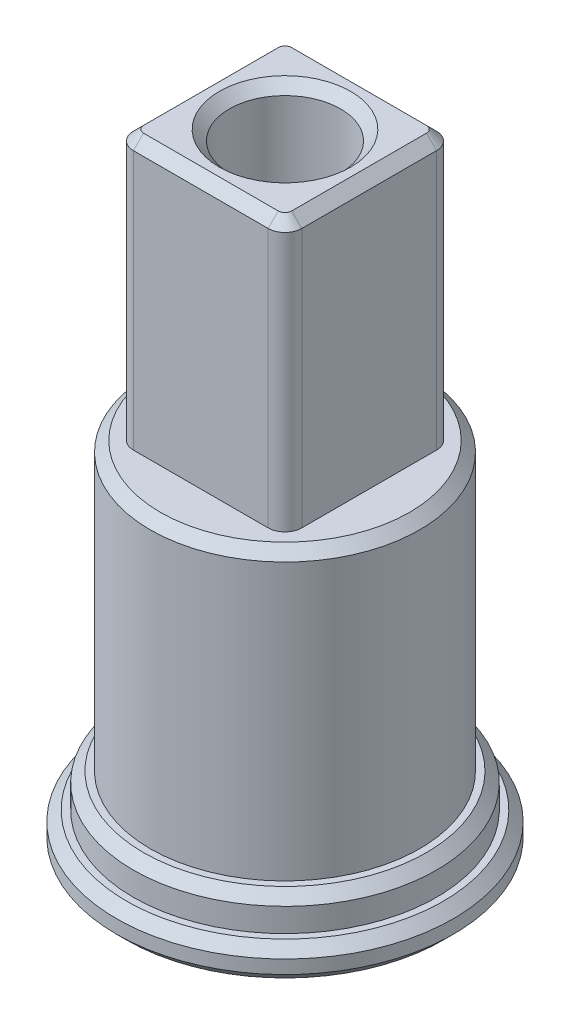
SolidWorks part; units mm, degrees
material "보통 탄소강"
ref_plane "정면" through (0, 0, 0) normal (0, 0, 1) x (1, 0, 0)
ref_plane "윗면" through (0, 0, 0) normal (0, 1, 0) x (1, 0, 0)
ref_plane "우측면" through (0, 0, 0) normal (1, 0, 0) x (0, 0, -1)
sketch "스케치1" plane through (0, 0, 0) normal (0, 1, 0) x (1, 0, 0)
  line L1 (2.5, -2.5) -> (-2.5, -2.5)
  line L2 (2.5, -2.5) -> (2.5, 2.5)
  line L3 (2.5, 2.5) -> (-2.5, 2.5)
  line L4 (-2.5, -2.5) -> (-2.5, 2.5)
  line L5 (2.5, -2.5) -> (-2.5, 2.5) construction
  line L6 (2.5, 2.5) -> (-2.5, -2.5) construction
  circle A0 centre (0, 0) radius 4
  circle A1 centre (0, 0) radius 5
  circle A2 centre (0, 0) radius 4.5
  dimension "D1" = 8
  dimension "D2" = 10
  dimension "D3" = 9
  dimension "D4" = 5
extrude "보스-돌출1" add sketch "스케치1" along normal blind 1 contours A1 A2 region at (-4.8586, 0, 0)
extrude "보스-돌출2" add sketch "스케치1<5>" along normal blind 2 contours A2 A0 region at (-4.3727, 0, 0)
sketch "스케치1<5>" plane through (0, 0, 0) normal (0, 1, 0) x (1, 0, 0) same geometry as "스케치1"
extrude "보스-돌출3" add sketch "스케치1<6>" along normal blind 10.5 contours A0 L1 L4 L3 L2 | L4 L1 L2 L3 region at (0, 0, 0) region at (-3.8869, 0, 0)
sketch "스케치1<6>" plane through (0, 0, 0) normal (0, 1, 0) x (1, 0, 0) same geometry as "스케치1"
extrude "보스-돌출4" add sketch "스케치1<7>" along normal blind 18.5 contours L4 L1 L2 L3 region at (0, 0, 0)
sketch "스케치1<7>" plane through (0, 0, 0) normal (0, 1, 0) x (1, 0, 0) same geometry as "스케치1"
sketch "스케치3" plane through (0, 0, 0) normal (0, -1, 0) x (1, 0, 0)
  line L0 (0, 1) -> (0, -1) construction
  line L1 (1, 1) -> (1, -1)
  line L2 (-1, 1) -> (-1, -1)
  arc A0 (1, 1) -> (-1, 1) centre (0, 1) ccw
  arc A1 (-1, -1) -> (1, -1) centre (0, -1) ccw
  point P3 (0, 0)
  dimension "D1" = 1
  dimension "D2" = 2
extrude "컷-돌출1" cut sketch "스케치3" against normal blind 1
sketch "스케치5" plane through (0, 18.5, 0) normal (0, 1, 0) x (1, 0, 0)
  circle A0 centre (0, 0) radius 1.65
  dimension "D1" = 3.3
sketch "스케치4" plane through (0, 0, 0) normal (0, 0, 1) x (1, 0, 0)
  line L0 (0, -0.5862) -> (0, 5.0613) construction
  line L1 (0, 8.5) -> (-1.65, 8.5)
  line L3 (-1.65, 8.5) -> (0, 7.8165)
  line L4 (0, 8.5) -> (0, 7.8165)
  line L5 (2.5, 18.5) -> (-2.5, 18.5) construction
  dimension "D1" = 67.5
  dimension "D2" = 1.65
  dimension "D3" = 10
revolve "컷-회전1" cut sketch "스케치4" angle 360 about L0
extrude "컷-돌출2" cut sketch "스케치5" against normal blind 10
fillet "필렛1" radius 0.5 4 edges at (2.5, 14.5, 2.5) (2.5, 14.5, -2.5) (-2.5, 14.5, 2.5) (-2.5, 14.5, -2.5)
chamfer "모따기1" distance 0.3 angle 45 13 edges at (0, 18.5, 1.65) (0, 0, 5) (0, 1, 5) (0, 2, 4.5) (0, 10.5, 4) (2.5, 18.5, 0) (0, 18.5, -2.5) (-2.5, 18.5, 0) (0, 18.5, 2.5) (2.3536, 18.5, 2.3536) (-2.3536, 18.5, 2.3536) (2.3536, 18.5, -2.3536) (-2.3536, 18.5, -2.3536)
